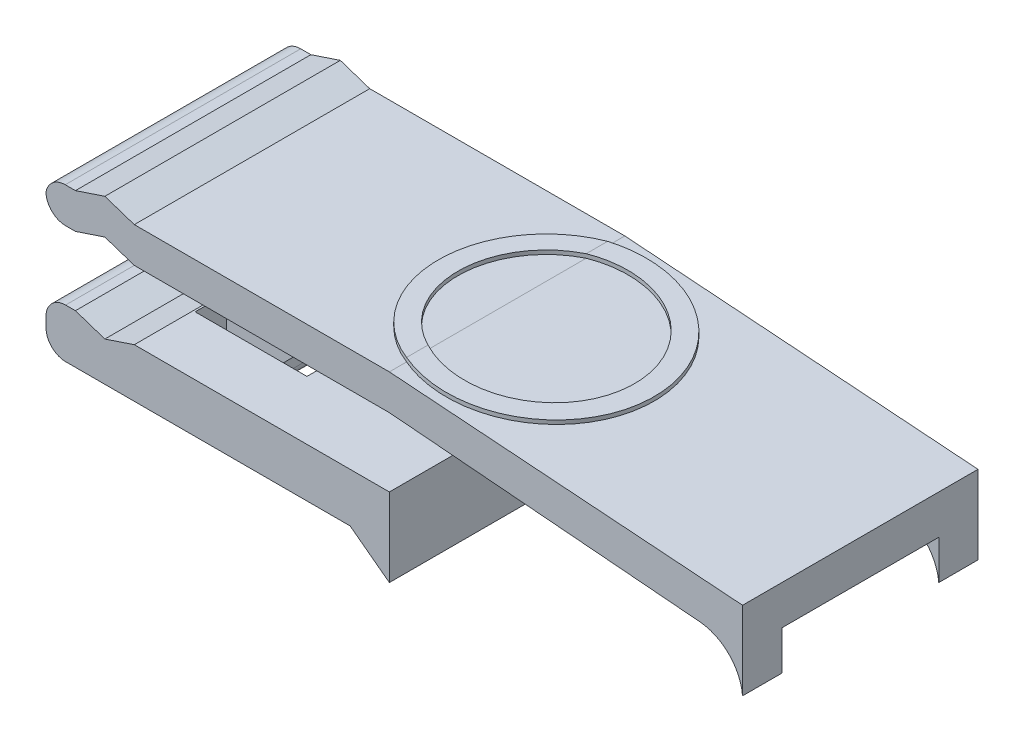
SolidWorks part; units mm, degrees
ref_plane "Front Plane" through (0, 0, 0) normal (0, 0, 1) x (1, 0, 0)
ref_plane "Top Plane" through (0, 0, 0) normal (0, 1, 0) x (1, 0, 0)
ref_plane "Right Plane" through (0, 0, 0) normal (1, 0, 0) x (0, 0, -1)
sketch "Sketch1" plane through (0, 0, 0) normal (0, 0, 1) x (1, 0, 0)
  line L0 (0, 0) -> (0, 4) construction
  line L1 (0, 0) -> (-18, 0) construction
  line L2 (0, 4) -> (-18, 5.3)
  line L3 (-18, 5.3) -> (-31, 5.3)
  line L4 (-31, 5.3) -> (-32.5, 5.8)
  line L5 (-32.5, 5.8) -> (-34, 5.3)
  line L6 (-34, 5.3) -> (-35.5, 5.3)
  line L7 (-35.5, 5.3) -> (-35.5, 3.5)
  line L8 (-35.5, -2.5) -> (-20, -2.5)
  line L9 (-20, -2.5) -> (-18, -4)
  line L10 (-35.5, 3.5) -> (-34, 3.5)
  line L11 (-34, 3.5) -> (-32.5, 4)
  line L12 (-18, 0) -> (-18, -4)
  line L13 (-18, 0) -> (-31, 0)
  line L14 (-31, 0) -> (-32.5, -0.5)
  line L15 (-32.5, -0.5) -> (-34, 0)
  line L16 (-34, 0) -> (-35.5, 0)
  line L17 (-35.5, 0) -> (-35.5, -2.5)
  line L18 (-32.5, 4) -> (-31, 3.5)
  line L19 (-31, 3.5) -> (-18, 3.5)
  line L20 (-18, 0) -> (-18, 5.3) construction
  line L21 (-18, 3.5) -> (0, 2)
  line L22 (0, 2) -> (0, 4)
  dimension "D1" = 13
  dimension "D2" = 18
  dimension "D3" = 0.5
  dimension "D4" = 2.5
  dimension "D5" = 1.5
  dimension "D6" = 3.5
  dimension "D7" = 1.5
  dimension "D8" = 2
  dimension "D9" = 0.5
  dimension "D10" = 2
  dimension "D11" = 0.5
  dimension "D12" = 1.8
  dimension "D13" = 1.5
  dimension "D15" = 3
  dimension "D16" = 1.5
extrude "Boss-Extrude1" add sketch "Sketch1" along normal blind 12
sketch "Sketch2" plane through (0, -2.5, 0) normal (0, -1, 0) x (1, 0, 0)
  line L0 (-20, 12) -> (-20, 0) construction
  line L1 (-30.9, 9) -> (-25.2, 9)
  line L2 (-30.9, 9) -> (-30.9, 3)
  line L3 (-30.9, 3) -> (-25.2, 3)
  line L4 (-25.2, 9) -> (-25.2, 3)
  line L5 (-31, 12) -> (-31, 0) construction
  line L7 (-20, 6) -> (-35.5, 6) construction
  line L8 (-35.5, 12) -> (-35.5, 0) construction
  point P9 (-25.2, 6)
  dimension "D1" = 0.1
  dimension "D2" = 5.7
  dimension "D3" = 6
extrude "Cut-Extrude1" cut sketch "Sketch2" against normal blind 3
sketch "Sketch3" plane through (0, 0, 3) normal (0, 0, 1) x (1, 0, 0)
  line L0 (-25.2, 0) -> (-27.2, -2)
  line L1 (-27.2, -2) -> (-27.2, -2.5)
  line L2 (-35.5, -2.5) -> (-20, -2.5) construction
  line L3 (-27.2, -2.5) -> (-25.2, -2.5)
  line L4 (-25.2, -2.5) -> (-25.2, 0)
  dimension "D1" = 0.5
  dimension "D2" = 2
extrude "Boss-Extrude2" add sketch "Sketch3" along normal up to surface (6 mm away) up to face at (-28.05, -1.25, 9)
sketch "Sketch4" plane through (0, 0, 12) normal (0, 0, 1) x (1, 0, 0)
  line L0 (-28.4, -2) -> (-26.4, 0)
  line L1 (-18, 0) -> (-31, 0) construction
  line L2 (-26.4, 0) -> (-26.4, 0.4)
  line L3 (-26.4, 0.4) -> (-27.9, 0.4)
  line L4 (-27.9, 0.4) -> (-27.9, 1.9)
  line L5 (-31, 3.5) -> (-18, 3.5) construction
  line L6 (-28.4, -2) -> (-28.4, -3)
  line L7 (-28.4, -3) -> (-29.8, -3)
  line L8 (-29.8, -3) -> (-29.8, 3.5)
  line L9 (-29.8, 3.5) -> (-26.3, 3.5)
  line L10 (-27.2, -2) -> (-27.2, -2.5) construction
  line L11 (-30.9, 0) -> (-30.9, -2.5) construction
  line L15 (-35.5, -2.5) -> (-20, -2.5) construction
  arc A1 (-27.9, 1.9) -> (-26.3, 3.5) centre (-26.3, 1.9) cw
  dimension "D1" = 1.5
  dimension "D2" = 1.2
  dimension "D3" = 45
  dimension "D4" = 0.4
  dimension "D5" = 1.4
  dimension "D6" = 1
  dimension "D7" = 2
  dimension "D8" = 1.5
  dimension "D9" = 1.1
  dimension "D11" = 0.8
  dimension "D13" = 2.9
  dimension "D14" = 3.1
extrude "Boss-Extrude3" add sketch "Sketch4" against normal mid plane 5 from offset 6 offset against normal yes
fillet "Fillet7" radius 1 1 edges at (-35.5, 0, 6)
fillet "Fillet8" radius 1 1 edges at (-35.5, 3.5, 6)
fillet "Fillet10" radius 1 1 edges at (-35.5, 5.3, 6)
fillet "Fillet11" radius 1 1 edges at (-35.5, -2.5, 6)
sketch "Sketch5" plane through (0, 0, 12) normal (0, 0, 1) x (1, 0, 0)
  line L0 (0, 2) -> (0, 0)
  line L1 (-18, 3.5) -> (0, 2) construction
  line L2 (-2.1818, 2.1818) -> (0, 2)
  arc A0 (-2.1818, 2.1818) -> (0, 0) centre (-2.3802, -0.1983) cw
extrude "Boss-Extrude4" add sketch "Sketch5" against normal blind 2
extrude "Boss-Extrude5" add sketch "Sketch5<2>" along normal blind 2 from offset 12 offset against normal yes
sketch "Sketch5<2>" plane through (0, 0, 12) normal (0, 0, 1) x (1, 0, 0) same geometry as "Sketch5"
fillet "Fillet12" radius 0.5 2 edges at (-28.4, -3, 6) (-29.8, -3, 6)
sketch "Sketch6" plane through (0, 0, 0) normal (0, 1, 0) x (1, 0, 0)
  line L2 (-18, -6) -> (-31, -6) construction
  line L3 (-18, -12) -> (-18, 0) construction
  line L4 (-31, -12) -> (-31, 0) construction
  circle A0 centre (-16, -6) radius 4.5
  circle A1 centre (-16, -6) radius 5.5
  dimension "D1" = 9
  dimension "D2" = 11
  dimension "D3" = 15
extrude "Boss-Extrude7" add sketch "Sketch6" against normal up to body from offset 5.5
sketch "Sketch7" plane through (0, 0, 0) normal (0, 0, 1) x (1, 0, 0)
  line L0 (-18, 5.5) -> (-8, 4.7778)
  line L3 (-8, 4.7778) -> (-8, 5.5)
  line L4 (-8, 5.5) -> (-18, 5.5)
  line L5 (0, 4) -> (-18, 5.3) construction
  line L6 (-11.5, 5.5) -> (-20.5, 5.5) construction
  dimension "D1" = 10
extrude "Cut-Extrude3" cut sketch "Sketch7" along normal through all
